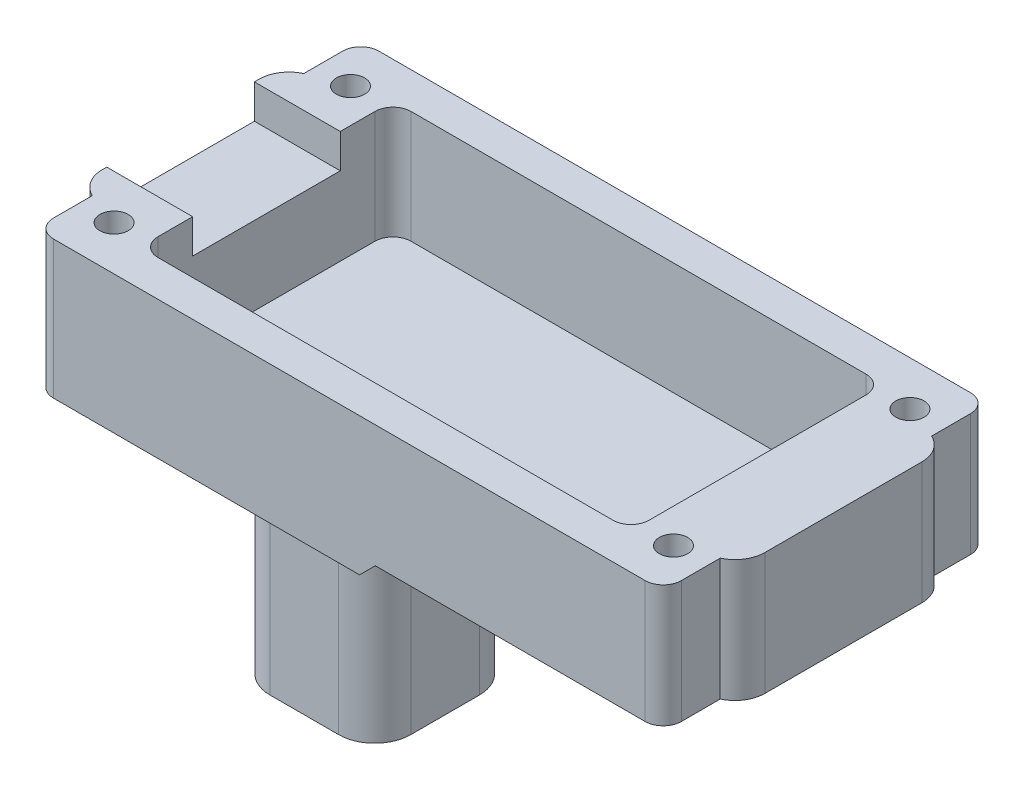
SolidWorks part; units mm, degrees
material "ABS"
ref_plane "Alzado" through (0, 0, 0) normal (0, 0, 1) x (1, 0, 0)
ref_plane "Planta" through (0, 0, 0) normal (0, 1, 0) x (1, 0, 0)
ref_plane "Vista lateral" through (0, 0, 0) normal (1, 0, 0) x (0, 0, -1)
sketch "Croquis1" plane through (0, 0, 0) normal (0, 1, 0) x (1, 0, 0)
  line L1 (1.5, 0) -> (50.6, 0)
  line L2 (0, 1.5) -> (0, 25.5)
  line L3 (1.5, 27) -> (50.6, 27)
  line L4 (52.1, 1.5) -> (52.1, 25.5)
  line L5 (7.175, 24) -> (44.925, 24)
  line L6 (5.675, 22.5) -> (5.675, 4.5)
  line L7 (7.175, 3) -> (44.925, 3)
  line L8 (46.425, 22.5) -> (46.425, 4.5)
  arc A0 (50.6, 0) -> (52.1, 1.5) centre (50.6, 1.5) ccw
  arc A1 (1.5, 0) -> (0, 1.5) centre (1.5, 1.5) cw
  arc A2 (50.6, 27) -> (52.1, 25.5) centre (50.6, 25.5) cw
  arc A3 (0, 25.5) -> (1.5, 27) centre (1.5, 25.5) cw
  arc A4 (5.675, 4.5) -> (7.175, 3) centre (7.175, 4.5) ccw
  arc A5 (44.925, 3) -> (46.425, 4.5) centre (44.925, 4.5) ccw
  arc A6 (44.925, 24) -> (46.425, 22.5) centre (44.925, 22.5) cw
  arc A7 (7.175, 24) -> (5.675, 22.5) centre (7.175, 22.5) ccw
  point P9 (0, 0)
  point P18 (26.05, 24)
  point P19 (26.05, 27)
  point P20 (46.425, 13.5)
  point P21 (52.1, 13.5)
  point P24 (5.675, 3)
  point P27 (46.425, 3)
  point P32 (5.675, 24)
  dimension "D3" = 1.5
  dimension "D6" = 1.5
  dimension "D1" = 52.1
  dimension "D2" = 27
  dimension "D4" = 21
  dimension "D5" = 40.75
extrude "Saliente-Extruir1" add sketch "Croquis1" along normal blind 9.33
sketch "Croquis2" plane through (0, 0, 0) normal (0, -1, 0) x (1, 0, 0)
  line L4 (50.6, 0) -> (1.5, 0)
  line L5 (0, -1.5) -> (0, -25.5)
  line L6 (1.5, -27) -> (50.6, -27)
  line L7 (52.1, -25.5) -> (52.1, -1.5)
  line L8 (50.6, 0) -> (1.5, 0)
  line L9 (0, -1.5) -> (0, -25.5)
  line L10 (1.5, -27) -> (50.6, -27)
  line L11 (52.1, -25.5) -> (52.1, -1.5)
  arc A4 (52.1, -1.5) -> (50.6, 0) centre (50.6, -1.5) ccw
  arc A5 (1.5, 0) -> (0, -1.5) centre (1.5, -1.5) ccw
  arc A6 (0, -25.5) -> (1.5, -27) centre (1.5, -25.5) ccw
  arc A7 (50.6, -27) -> (52.1, -25.5) centre (50.6, -25.5) ccw
  arc A8 (52.1, -1.5) -> (50.6, 0) centre (50.6, -1.5) ccw
  arc A9 (1.5, 0) -> (0, -1.5) centre (1.5, -1.5) ccw
  arc A10 (0, -25.5) -> (1.5, -27) centre (1.5, -25.5) ccw
  arc A11 (50.6, -27) -> (52.1, -25.5) centre (50.6, -25.5) ccw
  dimension "D1" = 0
extrude "Saliente-Extruir2" add sketch "Croquis2" along normal blind 1.5
sketch "Croquis3" plane through (0, 9.33, 0) normal (0, 1, 0) x (1, 0, 0)
  line L0 (50.6, 27) -> (1.5, 27) construction
  line L1 (0, 25.5) -> (0, 1.5) construction
  line L2 (26.05, 27) -> (26.05, 0) construction
  line L3 (1.5, 0) -> (50.6, 0) construction
  line L4 (0, 13.5) -> (52.1, 13.5) construction
  line L5 (52.1, 1.5) -> (52.1, 25.5) construction
  circle A0 centre (2.84, 23.31) radius 1.175
  circle A1 centre (49.26, 23.31) radius 1.175
  circle A2 centre (49.26, 3.69) radius 1.175
  circle A3 centre (2.84, 3.69) radius 1.175
  dimension "D1" = 2.35
  dimension "D2" = 3.69
  dimension "D3" = 2.84
extrude "Cortar-Extruir1" cut sketch "Croquis3" against normal through all
sketch "Croquis4" plane through (0, -1.5, 0) normal (0, -1, 0) x (1, 0, 0)
  line L0 (26.05, -27) -> (26.05, 0) construction
  line L1 (1.5, -27) -> (50.6, -27) construction
  line L2 (50.6, 0) -> (1.5, 0) construction
  line L3 (52.1, -13.5) -> (0, -13.5) construction
  line L4 (52.1, -25.5) -> (52.1, -1.5) construction
  line L5 (0, -1.5) -> (0, -25.5) construction
  line L6 (0, -13.5) -> (52.1, -13.5) construction
  circle A0 centre (49.26, -23.31) radius 2.025
  circle A1 centre (2.84, -23.31) radius 2.025
  circle A2 centre (2.84, -3.69) radius 2.025
  circle A3 centre (49.26, -3.69) radius 2.025
  dimension "D1" = 4.05
extrude "Cortar-Extruir2" cut sketch "Croquis4" against normal blind 2 draft 23
sketch "Croquis5" plane through (0, 9.33, 0) normal (0, 1, 0) x (1, 0, 0)
  line L0 (0, 22.27) -> (0, 4.73)
  line L1 (-1.45, 20) -> (-1.45, 7)
  line L2 (26.05, 27) -> (26.05, 0) construction
  line L3 (0, 25.5) -> (0, 1.5) construction
  line L4 (50.6, 27) -> (1.5, 27) construction
  line L5 (1.5, 0) -> (50.6, 0) construction
  line L6 (53.55, 20) -> (53.55, 7)
  line L7 (52.1, 22.27) -> (52.1, 4.73)
  arc A0 (-1.45, 7) -> (0, 4.73) centre (1.05, 6.9988) ccw
  arc A1 (0, 22.27) -> (-1.45, 20) centre (1.05, 20.0012) ccw
  arc A2 (52.1, 22.27) -> (53.55, 20) centre (51.05, 20.0012) cw
  arc A3 (53.55, 7) -> (52.1, 4.73) centre (51.05, 6.9988) cw
  point P8 (-1.45, 13.5)
  point P9 (0, 13.5)
  point P12 (0, 13.5)
  dimension "D1" = 5
  dimension "D2" = 5
  dimension "D3" = 17.54
  dimension "D4" = 13
  dimension "D5" = 1.45
extrude "Saliente-Extruir3" add sketch "Croquis5" against normal up to surface (10.83 mm away) up to face at (49.26, -1.5, -1.665)
sketch "Croquis6" plane through (5.675, 0, 0) normal (1, 0, 0) x (0, 0, -1)
  line L0 (22.5, 9.33) -> (4.5, 9.33) construction
  line L1 (7.375, 9.33) -> (19.625, 9.33)
  line L2 (7.375, 9.33) -> (7.375, 6.5)
  line L3 (7.375, 6.5) -> (19.625, 6.5)
  line L4 (19.625, 9.33) -> (19.625, 6.5)
  point P6 (13.5, 6.5)
  point P7 (13.5, 9.33)
  dimension "D1" = 2.83
  dimension "D2" = 12.25
extrude "Cortar-Extruir3" cut sketch "Croquis6" against normal through all
sketch "Croquis7" plane through (0, -1.5, 0) normal (0, -1, 0) x (1, 0, 0)
  line L0 (26.05, -27) -> (26.05, 0) construction
  line L1 (11.81, -19.35) -> (17.51, -19.35)
  line L2 (8.81, -16.35) -> (8.81, -10.65)
  line L3 (11.81, -7.65) -> (17.51, -7.65)
  line L4 (20.51, -16.35) -> (20.51, -10.65)
  line L5 (1.5, -27) -> (50.6, -27) construction
  line L6 (50.6, 0) -> (1.5, 0) construction
  line L8 (0, -1.5) -> (0, -4.73) construction
  arc A0 (17.51, -7.65) -> (20.51, -10.65) centre (17.51, -10.65) cw
  arc A1 (17.51, -19.35) -> (20.51, -16.35) centre (17.51, -16.35) ccw
  arc A2 (8.81, -10.65) -> (11.81, -7.65) centre (11.81, -10.65) cw
  arc A3 (11.81, -19.35) -> (8.81, -16.35) centre (11.81, -16.35) cw
  point P10 (20.51, -13.5)
  point P11 (26.05, -13.5)
  point P12 (14.66, -7.65)
  dimension "D4" = 3
  dimension "D1" = 11.7
  dimension "D2" = 11.7
  dimension "D3" = 14.66
extrude "Saliente-Extruir4" add sketch "Croquis7" along normal blind 20
sketch "Croquis8" plane through (0, 0, -27) normal (0, 0, -1) x (-1, 0, 0)
  line L0 (-1.5, -1.5) -> (-50.6, -1.5) construction
  line L1 (-53.55, -1.5) -> (-53.55, 9.33) construction
  line L2 (-53.55, -0.19) -> (-28.2, -0.19)
  line L3 (-53.55, -0.54) -> (-28.55, -0.54) construction
  line L4 (-53.55, -0.54) -> (-53.55, -1.5)
  line L5 (-53.55, -1.5) -> (-28.55, -1.5)
  line L6 (-28.55, -0.54) -> (-28.55, -1.5) construction
  line L7 (-28.2, -0.19) -> (-28.2, -1.5)
  line L8 (-53.55, -0.54) -> (-53.55, -0.19)
  line L9 (-28.55, -1.5) -> (-28.2, -1.5)
  circle A0 centre (-49.12, -9.54) radius 9 construction
  dimension "D1" = 18
  dimension "D2" = 8.04
  dimension "D3" = 4.43
  dimension "D4" = 25
  dimension "D5" = 0.35
extrude "Cortar-Extruir4" cut sketch "Croquis8" against normal up to surface (27 mm away) up to face at (26.05, 3.915, 0)
chamfer "Chaflán1" distance 1.3 angle 45 1 edges at (28.2, -1.5, -13.5)
sketch "Croquis10" plane through (0, 0, 0) normal (0, 1, 0) x (1, 0, 0)
  line L4 (5.675, 22.5) -> (5.675, 4.5)
  line L5 (7.175, 3) -> (44.925, 3)
  line L6 (46.425, 4.5) -> (46.425, 22.5)
  line L7 (44.925, 24) -> (7.175, 24)
  line L8 (5.675, 22.5) -> (5.675, 4.5)
  line L9 (7.175, 3) -> (44.925, 3)
  line L10 (46.425, 4.5) -> (46.425, 22.5)
  line L11 (44.925, 24) -> (7.175, 24)
  arc A4 (5.675, 4.5) -> (7.175, 3) centre (7.175, 4.5) ccw
  arc A5 (44.925, 3) -> (46.425, 4.5) centre (44.925, 4.5) ccw
  arc A6 (46.425, 22.5) -> (44.925, 24) centre (44.925, 22.5) ccw
  arc A7 (7.175, 24) -> (5.675, 22.5) centre (7.175, 22.5) ccw
  arc A8 (5.675, 4.5) -> (7.175, 3) centre (7.175, 4.5) ccw
  arc A9 (44.925, 3) -> (46.425, 4.5) centre (44.925, 4.5) ccw
  arc A10 (46.425, 22.5) -> (44.925, 24) centre (44.925, 22.5) ccw
  arc A11 (7.175, 24) -> (5.675, 22.5) centre (7.175, 22.5) ccw
  dimension "D1" = 0
extrude "Saliente-Extruir5" add sketch "Croquis10" along normal blind 0.61
sketch "Croquis11" plane through (0, 6.5, 0) normal (0, 1, 0) x (1, 0, 0)
  line L4 (5.675, 7.375) -> (5.675, 19.625)
  line L5 (5.675, 19.625) -> (-1.45, 19.625)
  line L6 (-1.45, 19.625) -> (-1.45, 7.375)
  line L7 (-1.45, 7.375) -> (5.675, 7.375)
  line L8 (5.675, 7.375) -> (5.675, 19.625)
  line L9 (5.675, 19.625) -> (-1.45, 19.625)
  line L10 (-1.45, 19.625) -> (-1.45, 7.375)
  line L11 (-1.45, 7.375) -> (5.675, 7.375)
  dimension "D1" = 0
extrude "Saliente-Extruir6" add sketch "Croquis11" along normal blind 0.61
sketch "Croquis12" plane through (0, 9.33, 0) normal (0, 1, 0) x (1, 0, 0)
  line L16 (5.675, 7.375) -> (-1.45, 7.375)
  line L17 (-1.45, 7.375) -> (-1.45, 7)
  line L18 (0, 4.73) -> (0, 1.5)
  line L19 (1.5, 0) -> (50.6, 0)
  line L20 (52.1, 1.5) -> (52.1, 4.73)
  line L21 (53.55, 7) -> (53.55, 20)
  line L22 (52.1, 22.27) -> (52.1, 25.5)
  line L23 (50.6, 27) -> (1.5, 27)
  line L24 (0, 25.5) -> (0, 22.27)
  line L25 (-1.45, 20) -> (-1.45, 19.625)
  line L26 (-1.45, 19.625) -> (5.675, 19.625)
  line L27 (5.675, 19.625) -> (5.675, 22.5)
  line L28 (7.175, 24) -> (44.925, 24)
  line L29 (46.425, 22.5) -> (46.425, 4.5)
  line L30 (44.925, 3) -> (7.175, 3)
  line L31 (5.675, 4.5) -> (5.675, 7.375)
  line L32 (5.675, 7.375) -> (-1.45, 7.375)
  line L33 (-1.45, 7.375) -> (-1.45, 7)
  line L34 (0, 4.73) -> (0, 1.5)
  line L35 (1.5, 0) -> (50.6, 0)
  line L36 (52.1, 1.5) -> (52.1, 4.73)
  line L37 (53.55, 7) -> (53.55, 20)
  line L38 (52.1, 22.27) -> (52.1, 25.5)
  line L39 (50.6, 27) -> (1.5, 27)
  line L40 (0, 25.5) -> (0, 22.27)
  line L41 (-1.45, 20) -> (-1.45, 19.625)
  line L42 (-1.45, 19.625) -> (5.675, 19.625)
  line L43 (5.675, 19.625) -> (5.675, 22.5)
  line L44 (7.175, 24) -> (44.925, 24)
  line L45 (46.425, 22.5) -> (46.425, 4.5)
  line L46 (44.925, 3) -> (7.175, 3)
  line L47 (5.675, 4.5) -> (5.675, 7.375)
  circle A0 centre (49.26, 23.31) radius 1.175 construction
  circle A1 centre (2.84, 23.31) radius 1.175 construction
  circle A2 centre (2.84, 3.69) radius 1.175 construction
  circle A3 centre (49.26, 3.69) radius 1.175 construction
  circle A4 centre (49.26, 3.69) radius 1.175
  circle A5 centre (2.84, 3.69) radius 1.175
  circle A6 centre (2.84, 23.31) radius 1.175
  circle A7 centre (49.26, 23.31) radius 1.175
  arc A12 (-1.45, 7) -> (0, 4.73) centre (1.05, 6.9988) ccw
  arc A13 (0, 1.5) -> (1.5, 0) centre (1.5, 1.5) ccw
  arc A14 (50.6, 0) -> (52.1, 1.5) centre (50.6, 1.5) ccw
  arc A15 (52.1, 4.73) -> (53.55, 7) centre (51.05, 6.9988) ccw
  arc A16 (53.55, 20) -> (52.1, 22.27) centre (51.05, 20.0012) ccw
  arc A17 (52.1, 25.5) -> (50.6, 27) centre (50.6, 25.5) ccw
  arc A18 (1.5, 27) -> (0, 25.5) centre (1.5, 25.5) ccw
  arc A19 (0, 22.27) -> (-1.45, 20) centre (1.05, 20.0012) ccw
  arc A20 (7.175, 24) -> (5.675, 22.5) centre (7.175, 22.5) ccw
  arc A21 (46.425, 22.5) -> (44.925, 24) centre (44.925, 22.5) ccw
  arc A22 (44.925, 3) -> (46.425, 4.5) centre (44.925, 4.5) ccw
  arc A23 (5.675, 4.5) -> (7.175, 3) centre (7.175, 4.5) ccw
  arc A24 (-1.45, 7) -> (0, 4.73) centre (1.05, 6.9988) ccw
  arc A25 (0, 1.5) -> (1.5, 0) centre (1.5, 1.5) ccw
  arc A26 (50.6, 0) -> (52.1, 1.5) centre (50.6, 1.5) ccw
  arc A27 (52.1, 4.73) -> (53.55, 7) centre (51.05, 6.9988) ccw
  arc A28 (53.55, 20) -> (52.1, 22.27) centre (51.05, 20.0012) ccw
  arc A29 (52.1, 25.5) -> (50.6, 27) centre (50.6, 25.5) ccw
  arc A30 (1.5, 27) -> (0, 25.5) centre (1.5, 25.5) ccw
  arc A31 (0, 22.27) -> (-1.45, 20) centre (1.05, 20.0012) ccw
  arc A32 (7.175, 24) -> (5.675, 22.5) centre (7.175, 22.5) ccw
  arc A33 (46.425, 22.5) -> (44.925, 24) centre (44.925, 22.5) ccw
  arc A34 (44.925, 3) -> (46.425, 4.5) centre (44.925, 4.5) ccw
  arc A35 (5.675, 4.5) -> (7.175, 3) centre (7.175, 4.5) ccw
  dimension "D1" = 0
extrude "Saliente-Extruir7" add sketch "Croquis12" along normal blind 0.61
sketch "Croquis13" plane through (0, -0.19, 0) normal (0, -1, 0) x (1, 0, 0)
  circle A0 centre (49.26, -3.69) radius 2.025
  dimension "D1" = 4.05
extrude "Cortar-Extruir5" cut sketch "Croquis13" against normal blind 3
sketch "Croquis14" plane through (0, -0.19, 0) normal (0, -1, 0) x (1, 0, 0)
  circle A0 centre (49.26, -23.31) radius 2.025
  dimension "D1" = 4.05
extrude "Cortar-Extruir6" cut sketch "Croquis14" against normal blind 3
sketch "Croquis15" plane through (0, 2.81, 0) normal (0, -1, 0) x (1, 0, 0)
  circle A1 centre (49.26, -3.69) radius 2.025
  circle A2 centre (49.26, -3.69) radius 2.025
  circle A3 centre (49.26, -23.31) radius 2.025
  circle A4 centre (49.26, -23.31) radius 2.025
  dimension "D1" = 0
  dimension "D2" = 0
extrude "Cortar-Extruir7" cut sketch "Croquis15" against normal blind 2 draft 23
sketch "Croquis16" plane through (0, -1.5, 0) normal (0, -1, 0) x (1, 0, 0)
  circle A0 centre (2.84, -23.31) radius 2.025 construction
  circle A1 centre (2.84, -3.69) radius 2.025 construction
  circle A2 centre (2.84, -23.31) radius 2.025
  circle A3 centre (2.84, -3.69) radius 2.025
extrude "Cortar-Extruir8" cut sketch "Croquis16" against normal blind 4.31
sketch "Croquis17" plane through (0, 2.81, 0) normal (0, -1, 0) x (1, 0, 0)
  circle A1 centre (2.84, -3.69) radius 2.025
  circle A2 centre (2.84, -3.69) radius 2.025
  circle A3 centre (2.84, -23.31) radius 2.025
  circle A4 centre (2.84, -23.31) radius 2.025
  dimension "D1" = 0
  dimension "D2" = 0
extrude "Cortar-Extruir9" cut sketch "Croquis17" against normal blind 2 draft 23
sketch "Croquis18" plane through (8.81, 0, 0) normal (-1, 0, 0) x (0, 0, 1)
  line L1 (-10.65, -21.5) -> (-16.35, -21.5) construction
  circle A0 centre (-13.5, -11.5) radius 2
  point P2 (-13.5, -21.5)
  dimension "D2" = 4
  dimension "D1" = 10
extrude "Cortar-Extruir10" cut sketch "Croquis18" against normal blind 2
